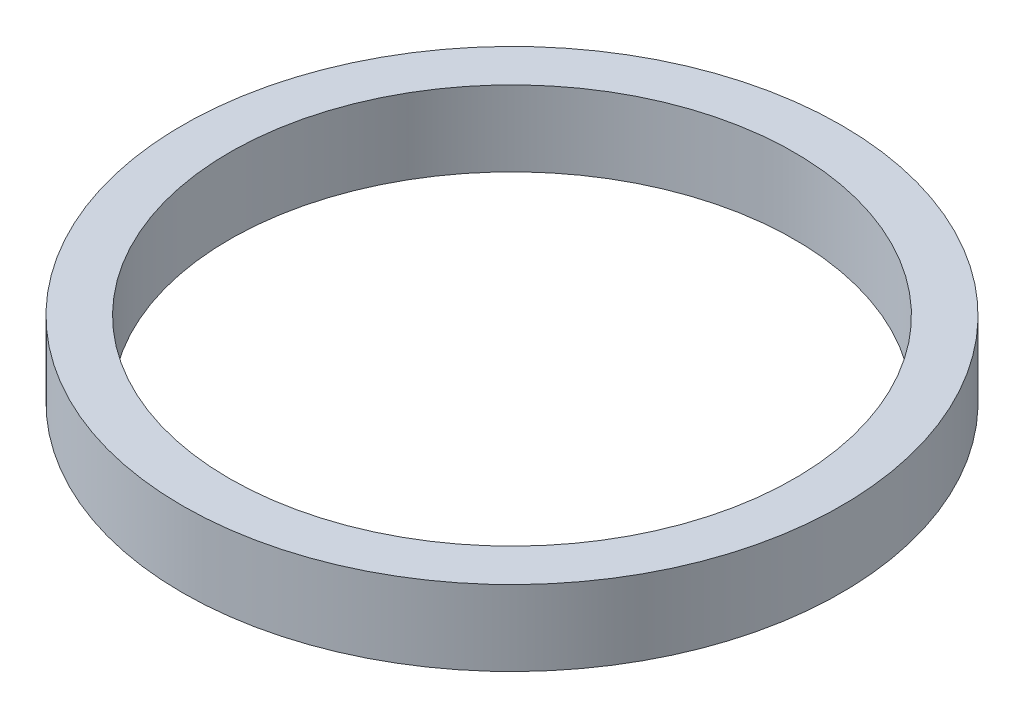
SolidWorks part; units mm, degrees
ref_plane "Front Plane" through (0, 0, 0) normal (0, 0, 1) x (1, 0, 0)
ref_plane "Top Plane" through (0, 0, 0) normal (0, 1, 0) x (1, 0, 0)
ref_plane "Right Plane" through (0, 0, 0) normal (1, 0, 0) x (0, 0, -1)
sketch "Sketch1" plane through (0, 0, 0) normal (0, 1, 0) x (1, 0, 0)
  circle A0 centre (0, 0) radius 52.5
  dimension "FLANGE_OD" = 105
extrude "Boss-Extrude1" add sketch "Sketch1" along normal blind 12
sketch "Sketch2" plane through (0, 0, 0) normal (0, 1, 0) x (1, 0, 0)
  circle A0 centre (0, 0) radius 45
  dimension "BORE_D" = 90
extrude "Cut-Extrude1" cut sketch "Sketch2" along normal through all
sketch "Sketch3" plane through (0, 12, 0) normal (0, 1, 0) x (1, 0, 0)
  circle A0 centre (0, 0) radius 24.7131 construction
  circle A1 centre (-24.7131, 0) radius 1.5
  dimension "BOLT_D" = 3
  dimension "BOLT_PCD" = 49.4262
extrude "Cut-Extrude2" cut sketch "Sketch3" against normal blind 11.5417 rebuild error yes
pattern_circular "CirPattern1" count 4 over 360 rebuild error yes
